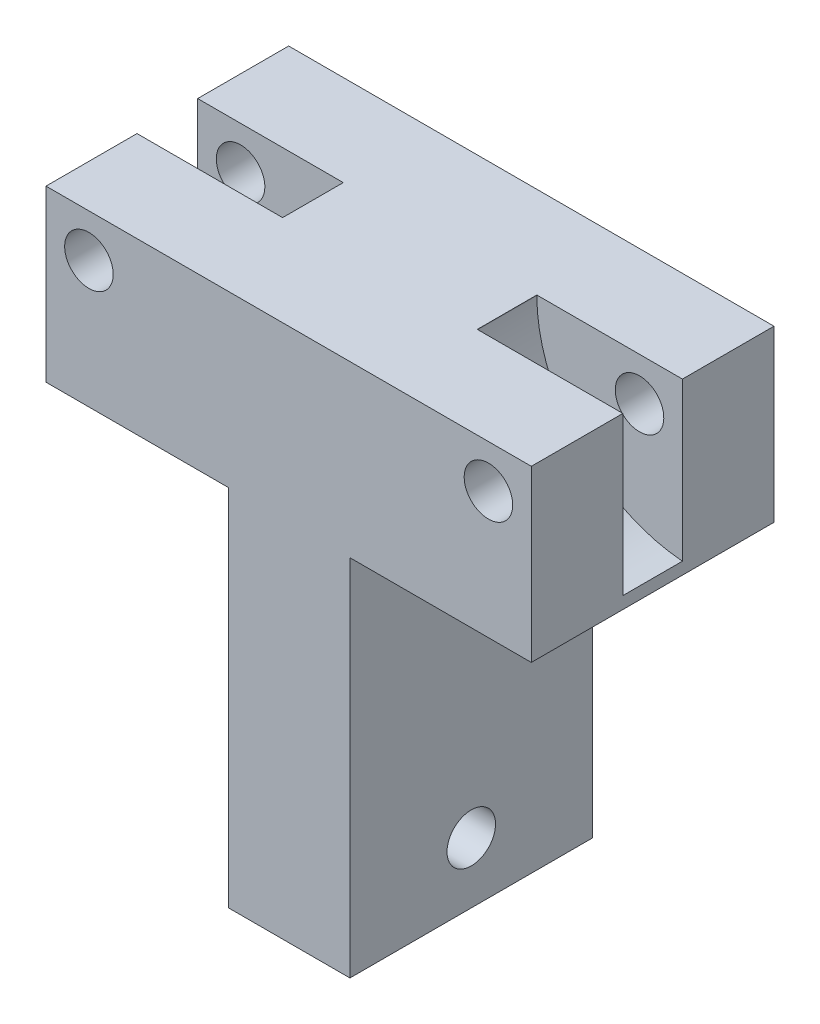
SolidWorks part; units mm, degrees
ref_plane "Alzado" through (0, 0, 0) normal (0, 0, 1) x (1, 0, 0)
ref_plane "Planta" through (0, 0, 0) normal (0, 1, 0) x (1, 0, 0)
ref_plane "Vista lateral" through (0, 0, 0) normal (1, 0, 0) x (0, 0, -1)
sketch "Croquis2" plane through (0, 0, 0) normal (0, 1, 0) x (1, 0, 0)
  line L0 (-2.5, 0) -> (2.5, 0)
  line L1 (-2.5, 0) -> (-2.5, 10)
  line L2 (-2.5, 10) -> (2.5, 10)
  line L3 (2.5, 10) -> (2.5, 0)
  point P4 (0, 0)
  dimension "D1" = 5
  dimension "D2" = 10
extrude "Saliente-Extruir1" add sketch "Croquis2" along normal blind 15
sketch "Croquis3" plane through (2.5, 0, 0) normal (1, 0, 0) x (0, 0, -1)
  line L0 (5, 0) -> (5, 2.5) construction
  line L1 (0, 0) -> (10, 0) construction
  circle A0 centre (5, 2.5) radius 1
  dimension "D2" = 2
  dimension "D1" = 2.5
extrude "Cortar-Extruir1" cut sketch "Croquis3" against normal through all
sketch "Croquis4" plane through (0, 15, 0) normal (0, 1, 0) x (1, 0, 0)
  line L0 (-10.0248, 10) -> (9.9752, 10)
  line L2 (9.9752, 10) -> (9.9752, 0)
  line L3 (9.9752, 0) -> (-10.0248, 0)
  line L4 (-10.0248, 0) -> (-10.0248, 10)
  point P3 (-0.0248, 10)
  dimension "D1" = 20
  dimension "D2" = 10
extrude "Saliente-Extruir2" add sketch "Croquis4" along normal blind 7
sketch "Croquis5" plane through (-10.0248, 0, 0) normal (-1, 0, 0) x (0, 0, 1)
  line L1 (-6.25, 22) -> (-3.75, 22)
  line L10 (-10, 22) -> (0, 22) construction
  line L11 (-3.75, 22) -> (-3.75, 15.5)
  line L12 (-3.75, 15.5) -> (-6.25, 15.5)
  line L13 (-6.25, 15.5) -> (-6.25, 22)
  point P5 (-5, 22)
  point P6 (-5, 22)
  dimension "D1" = 2.5
  dimension "D2" = 6.5
extrude "Cortar-Extruir2" cut sketch "Croquis5" against normal blind 6
sketch "Croquis6" plane through (0, 0, -10) normal (0, 0, -1) x (-1, 0, 0)
  line L0 (10.0248, 22) -> (8.2571, 20.2322) construction
  line L1 (10.0248, 22) -> (10.0248, 15) construction
  circle A0 centre (8.2571, 20.2322) radius 1
  dimension "D2" = 2
  dimension "D1" = 2.5
  dimension "D3" = 45
extrude "Cortar-Extruir3" cut sketch "Croquis6" against normal through all
sketch "Croquis7" plane through (9.9752, 0, 0) normal (1, 0, 0) x (0, 0, -1)
  line L1 (3.7733, 22) -> (6.2267, 22)
  line L6 (0, 22) -> (10, 22) construction
  line L7 (6.2267, 22) -> (6.2267, 15.5)
  line L10 (3.7733, 22) -> (3.7733, 15.5)
  line L11 (3.7733, 15.5) -> (6.2267, 15.5)
  point P0 (5, 22)
  point P7 (5, 22)
  dimension "D1" = 2.4533
  dimension "D2" = 6.5
extrude "Cortar-Extruir4" cut sketch "Croquis7" against normal blind 6
sketch "Croquis8" plane through (0, 0, -10) normal (0, 0, -1) x (-1, 0, 0)
  line L0 (-9.9752, 22) -> (-8.2074, 20.2322) construction
  line L1 (-9.9752, 22) -> (-9.9752, 15) construction
  circle A0 centre (-8.2074, 20.2322) radius 1
  dimension "D2" = 2
  dimension "D1" = 2.5
  dimension "D3" = 45
extrude "Cortar-Extruir5" cut sketch "Croquis8" against normal through all
fillet "Redondeo1" radius 6.5 2 edges at (-4.0248, 15.5, -5) (3.9752, 15.5, -5)
